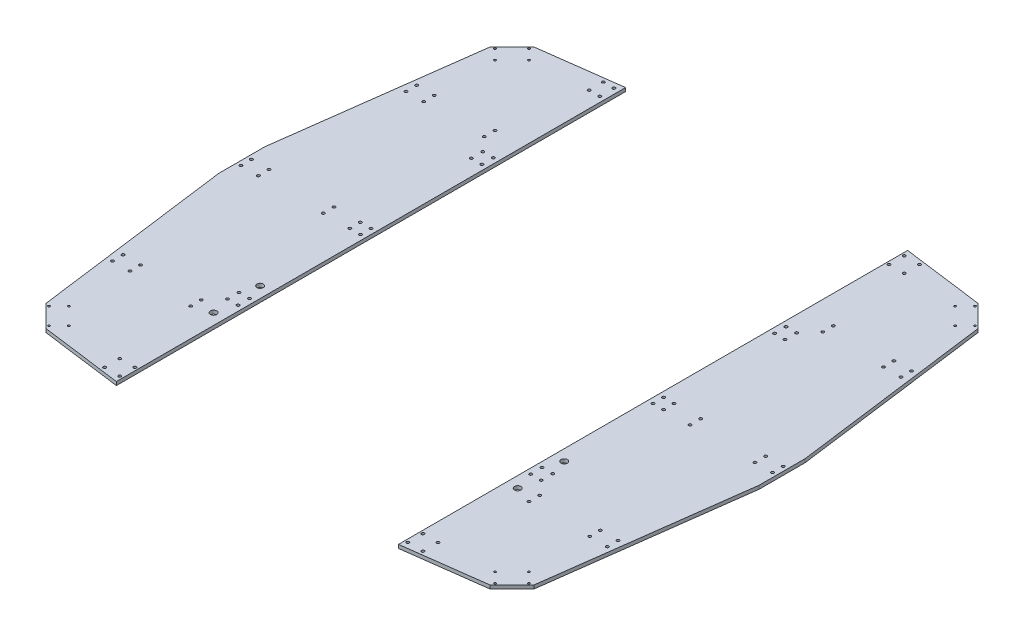
SolidWorks part; units mm, degrees
ref_plane "前视基准面" through (0, 0, 0) normal (0, 0, 1) x (1, 0, 0)
ref_plane "上视基准面" through (0, 0, 0) normal (0, 1, 0) x (1, 0, 0)
ref_plane "右视基准面" through (0, 0, 0) normal (1, 0, 0) x (0, 0, -1)
other "Configuration Table"
sketch "草图1" plane through (0, 0, 0) normal (0, 1, 0) x (1, 0, 0)
  line L0 (-314.9222, 345.9222) -> (-345.9222, 314.9222)
  line L5 (325, -325) -> (-325, 325) construction
  line L6 (325, 325) -> (-325, -325) construction
  line L7 (0, 325) -> (0, -325) construction
  line L8 (-383.07, 0) -> (383.0748, 0) construction
  line L9 (314.9222, 345.9222) -> (32.7201, 383.0748)
  line L10 (314.9222, 345.9222) -> (345.9222, 314.9222)
  line L11 (-383.07, 13.0001) -> (-230, 13.0001) construction
  line L12 (-314.9222, 345.9222) -> (-32.7201, 383.0748)
  line L13 (0, 325) -> (0, 399.6983)
  line L14 (-32.7201, 383.0748) -> (32.7201, 383.0748)
  line L15 (314.9222, -345.9222) -> (32.7201, -383.0748)
  line L16 (-32.7201, -383.0748) -> (32.7201, -383.0748)
  line L17 (-314.9222, -345.9222) -> (-32.7201, -383.0748)
  line L18 (-314.9222, -345.9222) -> (-345.9222, -314.9222)
  line L19 (-345.9222, 314.9222) -> (-383.0748, 32.7201)
  line L20 (-383.0748, -32.7201) -> (-383.0748, 32.7201)
  line L21 (-345.9222, -314.9222) -> (-383.0748, -32.7201)
  line L22 (-345.9222, -314.9222) -> (-314.9222, -345.9222)
  line L23 (345.9222, -314.9222) -> (314.9222, -345.9222)
  line L24 (345.9222, -314.9222) -> (383.0748, -32.7201)
  line L25 (383.0748, 32.7201) -> (383.0748, -32.7201)
  line L26 (345.9222, 314.9222) -> (383.0748, 32.7201)
  line L27 (-383.07, -12.9999) -> (-230, -12.9999) construction
  line L29 (361.6863, 195.182) -> (230, 195.182) construction
  line L30 (358.2633, 221.182) -> (230, 221.182) construction
  line L31 (-358.2633, 221.182) -> (-230, 221.182) construction
  line L32 (-361.6863, 195.182) -> (-230, 195.182) construction
  line L33 (361.6863, -195.182) -> (230, -195.182) construction
  line L34 (358.2633, -221.182) -> (230, -221.182) construction
  line L35 (-361.6863, -195.182) -> (-230, -195.182) construction
  line L36 (-358.2633, -221.182) -> (-230, -221.182) construction
  line L37 (-228, -357.3657) -> (-228, 357.3618) construction
  line L38 (-202, -360.7887) -> (-202, 360.7847) construction
  line L39 (383.07, 13.0001) -> (230, 13.0001) construction
  circle A5 centre (0, 0) radius 250
  circle A6 centre (302.1379, 326.1795) radius 1.5
  circle A7 centre (316.28, 340.3217) radius 1.5
  circle A8 centre (340.3217, 316.28) radius 1.5
  circle A9 centre (326.1795, 302.1379) radius 1.5
  circle A10 centre (302.1379, -326.1795) radius 1.5
  circle A11 centre (316.28, -340.3217) radius 1.5
  circle A12 centre (326.1795, -302.1379) radius 1.5
  circle A13 centre (340.3217, -316.28) radius 1.5
  circle A14 centre (-326.1795, -302.1379) radius 1.5
  circle A15 centre (-340.3217, -316.28) radius 1.5
  circle A16 centre (-302.1379, -326.1795) radius 1.5
  circle A17 centre (-316.28, -340.3217) radius 1.5
  circle A18 centre (-302.1379, 326.1795) radius 1.5
  circle A19 centre (-316.28, 340.3217) radius 1.5
  circle A20 centre (-326.1795, 302.1379) radius 1.5
  circle A21 centre (-340.3217, 316.28) radius 1.5
  circle A22 centre (350.9184, 215.682) radius 2
  circle A23 centre (377.0748, 7.5001) radius 2
  circle A24 centre (350.9184, 200.682) radius 2
  circle A25 centre (325.9184, 215.682) radius 2
  circle A26 centre (325.9184, 200.682) radius 2
  circle A27 centre (377.0748, -7.5951) radius 2
  circle A28 centre (352.0748, 7.5001) radius 2
  circle A29 centre (352.0748, -7.5951) radius 2
  circle A30 centre (350.9184, -200.682) radius 2
  circle A31 centre (350.9184, -215.682) radius 2
  circle A32 centre (325.9184, -200.682) radius 2
  circle A33 centre (325.9184, -215.682) radius 2
  circle A34 centre (-350.9184, -200.682) radius 2
  circle A35 centre (-325.9184, -200.682) radius 2
  circle A36 centre (-350.9184, -215.682) radius 2
  circle A37 centre (-325.9184, -215.682) radius 2
  circle A38 centre (-377.0748, 7.5001) radius 2
  circle A39 centre (-352.0748, 7.5001) radius 2
  circle A40 centre (-377.0748, -7.4999) radius 2
  circle A41 centre (-352.0748, -7.4999) radius 2
  circle A42 centre (-350.9184, 215.682) radius 2
  circle A43 centre (-350.9184, 200.682) radius 2
  circle A44 centre (-325.9184, 215.682) radius 2
  circle A45 centre (-325.9184, 200.682) radius 2
  circle A46 centre (-222.5, -164.8255) radius 2
  circle A47 centre (-207.5, -164.8255) radius 2
  circle A48 centre (-222.5, -181.0301) radius 2
  circle A49 centre (-207.5, -181.0301) radius 2
  circle A50 centre (-222.5, 181.0301) radius 2
  circle A51 centre (-207.5, 164.8255) radius 2
  circle A52 centre (-222.5, 164.8255) radius 2
  circle A53 centre (-207.5, 181.0301) radius 2
  circle A54 centre (207.5, -164.8255) radius 2
  circle A55 centre (222.5, -164.8255) radius 2
  circle A56 centre (207.5, -181.0301) radius 2
  circle A57 centre (222.5, -181.0301) radius 2
  circle A58 centre (207.5, 164.8255) radius 2
  circle A59 centre (222.5, 164.8255) radius 2
  circle A60 centre (207.5, 181.0301) radius 2
  circle A61 centre (222.5, 181.0301) radius 2
  circle A62 centre (-240, 215.682) radius 2
  circle A63 centre (-240, 200.682) radius 2
  circle A64 centre (-260, 7.5) radius 2
  circle A65 centre (-260, -7.5) radius 2
  circle A66 centre (-240, -200.682) radius 2
  circle A67 centre (-240, -215.682) radius 2
  circle A68 centre (240, -215.682) radius 2
  circle A69 centre (240, -200.682) radius 2
  circle A72 centre (240, 200.682) radius 2
  circle A73 centre (240, 215.682) radius 2
  circle A74 centre (207.5, 9.4052) radius 2
  circle A75 centre (222.5, 9.4052) radius 2
  circle A76 centre (207.5, -5.5948) radius 2
  circle A77 centre (222.5, -5.5948) radius 2
  circle A78 centre (-222.5, -5.5948) radius 2
  circle A79 centre (-207.5, -5.5948) radius 2
  circle A80 centre (-222.5, 9.4052) radius 2
  circle A81 centre (-207.5, 9.4052) radius 2
  circle A82 centre (260, -7.5) radius 2
  circle A83 centre (260, 7.5) radius 2
  circle A84 centre (215.6127, -141.5543) radius 4.5
  circle A85 centre (215.6127, -207.5543) radius 4.5
  circle A86 centre (-215.6127, -207.5543) radius 4.5
  circle A87 centre (-215.6127, -141.5543) radius 4.5
  point P0 (0, 0)
  point P13 (0, 383.0748)
  point P24 (-330.4222, -330.4222)
  point P75 (0, 0)
  point P192 (0, 0)
  point P195 (0, 0)
  dimension "D6" = 25
  dimension "D7" = 15
  dimension "D8" = 500
  dimension "D5" = 4
  dimension "D13" = 6
  dimension "D14" = 6
  dimension "D15" = 6
  dimension "D16" = 6
  dimension "D17" = 25
  dimension "D20" = 8
  dimension "D21" = 25
  dimension "D23" = 8
  dimension "D28" = 5.5
  dimension "D29" = 5.5
  dimension "D30" = 5.5
  dimension "D31" = 5.5
  dimension "D32" = 5.5
  dimension "D33" = 5.5
  dimension "D35" = 5.5
  dimension "D37" = 5.5
  dimension "D1" = 650
  dimension "D2" = 650
  dimension "D3" = 31
  dimension "D4" = 142.5
  dimension "D9" = 5.5
  dimension "D10" = 5.5
  dimension "D11" = 25
  dimension "D12" = 25
  dimension "D22" = 25
  dimension "D24" = 25
  dimension "D25" = 25
  dimension "D26" = 25
  dimension "D27" = 5.5
  dimension "D34" = 5.5
  dimension "D36" = 5.5
  dimension "D38" = 7.5001
  dimension "D39" = 7.4999
  dimension "D40" = 7.5
  dimension "D41" = 7.5
extrude "凸台-拉伸2" add sketch "草图1" along normal blind 5 contours L26 L10 L9 L14 L12 L0 L19 L20 L21 L18 L17 L16 L15 L23 L24 L25 | A13 L22 | L22 | A13 L18 region at (-172.4069, 0, -353.7562)
sketch "草图2" plane through (0, 5, 0) normal (0, 1, 0) x (1, 0, 0)
  line L0 (0, 0) -> (-330.4222, -330.4222) construction
  line L1 (0, 383.0748) -> (0, -383.0748)
  line L2 (-32.7201, 383.0748) -> (32.7201, 383.0748) construction
  line L3 (-32.7201, -383.0748) -> (32.7201, -383.0748) construction
  line L4 (-200, 361.052) -> (-200, -361.052)
  line L5 (-314.9222, 345.9222) -> (-32.7201, 383.0748) construction
  line L6 (-314.9222, -345.9222) -> (-32.7201, -383.0748) construction
  line L7 (200, 361.052) -> (200, -361.052)
  line L8 (314.9222, 345.9222) -> (32.7201, 383.0748) construction
  line L9 (314.9222, -345.9222) -> (32.7201, -383.0748) construction
  line L10 (-200, 361.052) -> (-200, 484.7149)
  line L11 (-200, 484.7149) -> (200, 484.7149)
  line L12 (200, 484.7149) -> (200, 361.052)
  line L13 (-200, -361.052) -> (-200, -418.819)
  line L14 (-200, -418.819) -> (200, -418.819)
  line L15 (200, -418.819) -> (200, -361.052)
  dimension "D1" = 200
  dimension "D2" = 200
extrude "切除-拉伸1" cut sketch "草图2" against normal blind 122 and the other way through all contours L4 L1 | L7 L1 | L7 L1 | L4 L1 | L0 L4 region at (-190.1188, 5, -422.8834)
sketch "草图3" plane through (0, 0, 0) normal (0, -1, 0) x (-1, 0, 0)
  circle A0 centre (225.7527, -352.0225) radius 2
  circle A1 centre (204.2473, -352.0225) radius 2
  circle A2 centre (225.7527, -330.517) radius 2
  circle A3 centre (204.2473, -330.517) radius 2
extrude "切除-拉伸2" cut sketch "草图3" along normal through all and the other way blind 39 contours A0 | A1 | A2 | A3
sketch "草图4" plane through (0, 5, 0) normal (0, 1, 0) x (1, 0, 0)
  line L0 (-222.5, 352.0186) -> (-207.5, 352.0186)
  line L1 (-215, 352.0186) -> (-215, 337.3883)
  line L2 (-228, -357.3657) -> (-228, 357.3618) construction
  line L3 (-202, -360.7887) -> (-202, 360.7847) construction
  line L4 (-228, -357.3657) -> (-228, 357.3618)
  line L5 (-202, -360.7887) -> (-202, 360.7847)
  line L6 (-202, 337.3883) -> (-228, 337.3883)
  circle A0 centre (-222.5, 352.0186) radius 2
  circle A1 centre (-207.5, 352.0186) radius 2
  circle A2 centre (-222.5, 332.0186) radius 2
  circle A3 centre (-207.5, 332.0186) radius 2
  circle A4 centre (204.2473, 330.5131) radius 2
  circle A5 centre (225.7527, 330.5131) radius 2
  circle A6 centre (204.2473, 352.0186) radius 2
  circle A7 centre (225.7527, 352.0186) radius 2
  circle A8 centre (204.2473, -352.0225) radius 2
  circle A9 centre (225.7527, -352.0225) radius 2
  circle A10 centre (204.2473, -330.517) radius 2
  circle A11 centre (225.7527, -330.517) radius 2
  dimension "D1" = 4
  dimension "D2" = 15
  dimension "D3" = 20
extrude "切除-拉伸3" cut sketch "草图4" against normal through all and the other way blind 20 contours A8 | A9 | A11 | A4 | A6 | A5 | A7 | A1 | A0 | A2 | A3 | A10 region at (-207.5, 5, -353.962) region at (-224.4434, 5, -352.0186) region at (-222.5, 5, -332.0186) region at (-207.5, 5, -332.0186) region at (204.2473, 5, -330.5131) region at (225.7527, 5, -330.5131) region at (204.2473, 5, -352.0186) region at (225.7527, 5, -352.0186) region at (204.2473, 5, 352.0225) region at (225.7527, 5, 352.0225) region at (225.7527, 5, 330.517)
sketch "草图5" plane through (0, 5, 0) normal (0, 1, 0) x (1, 0, 0)
  line L0 (-200, 150) -> (-200, -150)
  line L1 (200, 150) -> (200, -150)
  line L2 (-260, 7.5) -> (-260, -7.5) construction
  line L3 (-260, -7.5) -> (-200, -7.5) construction
  line L4 (-200, -7.5) -> (-200, 7.5)
  line L5 (-200, 7.5) -> (-260, 7.5) construction
  line L6 (-228, -357.3657) -> (-228, 357.3618) construction
  line L7 (-202, -360.7887) -> (-202, 360.7847) construction
  line L8 (0, 250) -> (0, -250) construction
  line L9 (-200, 361.048) -> (-200, -361.052) construction
  circle A0 centre (0, 0) radius 250
  circle A1 centre (-222.5, 7.5) radius 2
  circle A2 centre (-207.5, 7.5) radius 2
  circle A3 centre (-222.5, -7.5) radius 2
  circle A4 centre (-207.5, -7.5) radius 2
  circle A5 centre (207.5, -7.5) radius 2
  circle A6 centre (222.5, -7.5) radius 2
  circle A7 centre (207.5, 7.5) radius 2
  circle A8 centre (222.5, 7.5) radius 2
  dimension "D1" = 5.5
  dimension "D2" = 5.5
  dimension "D3" = 5.5
  dimension "D4" = 5.5
extrude "凸台-拉伸3" add sketch "草图5" against normal blind 5 contours L0 | L1 A0 region at (-220.2076, 5, 0) region at (220.2076, 5, 0)
